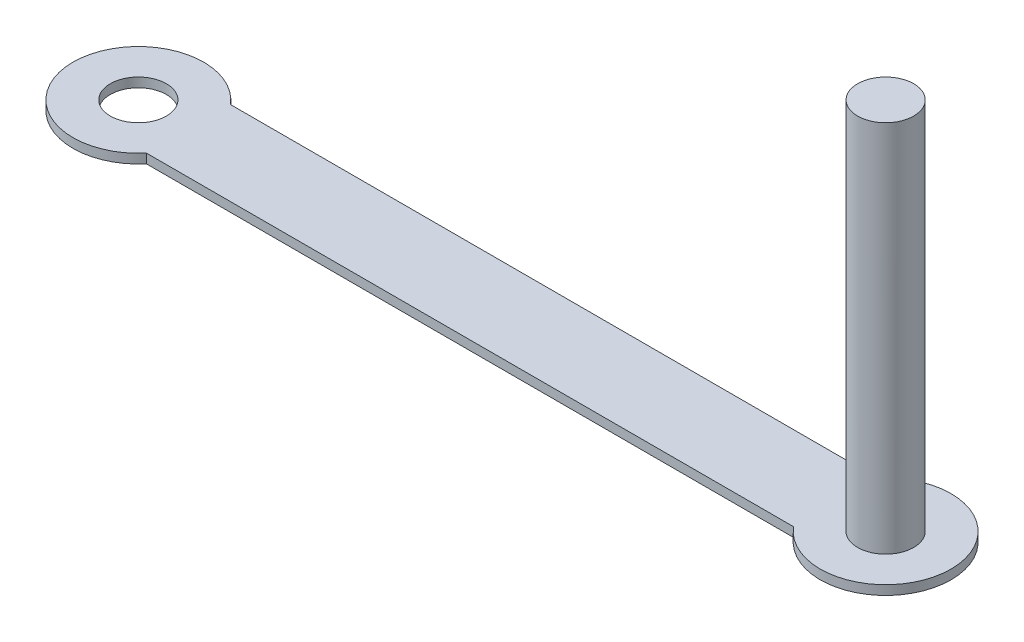
SolidWorks part; units mm, degrees
ref_plane "Front Plane" through (0, 0, 0) normal (0, 0, 1) x (1, 0, 0)
ref_plane "Top Plane" through (0, 0, 0) normal (0, 1, 0) x (1, 0, 0)
ref_plane "Right Plane" through (0, 0, 0) normal (1, 0, 0) x (0, 0, -1)
sketch "Sketch1" plane through (0, 0, 0) normal (0, 1, 0) x (1, 0, 0)
  line L0 (109.976, 14.2875) -> (-109.976, 14.2875)
  line L1 (-109.976, -14.2875) -> (109.976, -14.2875)
  line L3 (-149.117, 0) -> (199.2814, 0) construction
  arc A0 (109.976, -14.2875) -> (109.976, 14.2875) centre (127, 0) ccw
  arc A1 (-109.976, -14.2875) -> (-109.976, 14.2875) centre (-127, 0) cw
  circle A2 centre (-127, 0) radius 9.525
  dimension "D1" = 22.225
  dimension "D3" = 22.225
  dimension "D6" = 14.2875
  dimension "D8" = 19.05
  dimension "D2" = 28.575
  dimension "D4" = 127
  dimension "D5" = 127
extrude "Boss-Extrude1" add sketch "Sketch1" along normal blind 3.175
sketch "Sketch2" plane through (0, 3.175, 0) normal (0, 1, 0) x (1, 0, 0)
  circle A0 centre (127, 0) radius 9.525
  dimension "D1" = 19.05
extrude "Boss-Extrude2" add sketch "Sketch2" along normal blind 127
sketch "Sketch5" plane through (0, 0, 0) normal (0, 0, 1) x (1, 0, 0)
  line L0 (-101.6, 0) -> (101.6, -31.75)
  line L1 (-109.976, 0) -> (109.976, 0) construction
  line L2 (101.6, -31.75) -> (101.6, 0)
  dimension "D1" = 101.6
  dimension "D2" = 101.6
  dimension "D3" = 31.75
